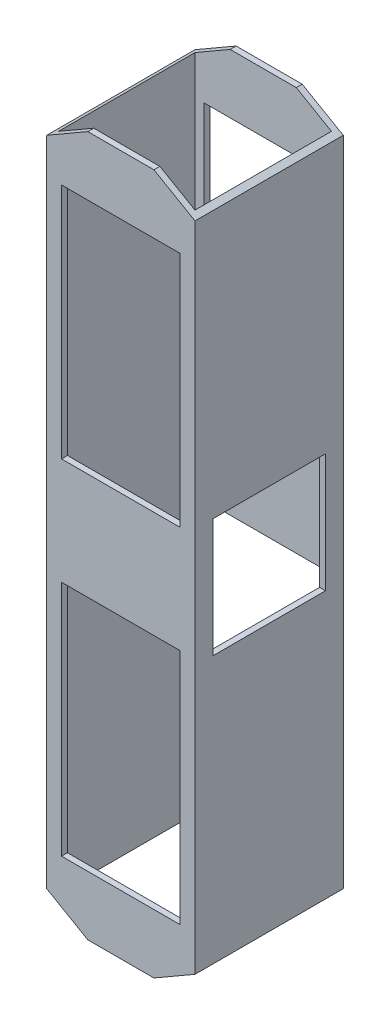
SolidWorks part; units mm, degrees
ref_plane "Alzado" through (0, 0, 0) normal (0, 0, 1) x (1, 0, 0)
ref_plane "Planta" through (0, 0, 0) normal (0, 1, 0) x (1, 0, 0)
ref_plane "Vista lateral" through (0, 0, 0) normal (1, 0, 0) x (0, 0, -1)
sketch "Croquis1" plane through (0, 0, 0) normal (0, 0, 1) x (1, 0, 0)
  line L0 (-35.0559, -98.8768) -> (-35.0559, 19.1232)
  line L3 (-35.0559, -98.8768) -> (-10.0559, -98.8768)
  line L4 (-10.0559, 19.1232) -> (-10.0559, -98.8768)
  line L5 (-35.0559, 19.1232) -> (-10.0559, 19.1232)
extrude "Saliente-Extruir1" add sketch "Croquis1" along normal blind 25
shell "Vaciado1" thickness 1 removed face at (-22.5559, -98.8768, 12.5) removed face at (-22.5559, 19.1232, 12.5)
sketch "Croquis2" plane through (0, 0, 25) normal (0, 0, 1) x (1, 0, 0)
  line L0 (-12.5559, -30.8768) -> (-32.5559, -30.8768)
  line L2 (-12.5559, -88.8768) -> (-12.5559, -48.8768)
  line L4 (-12.5559, -48.8768) -> (-32.5559, -48.8768)
  line L5 (-32.5559, -48.8768) -> (-32.5559, -88.8768)
  line L6 (-32.5559, -88.8768) -> (-22.5559, -88.8768)
  line L10 (-22.5559, -88.8768) -> (-12.5559, -88.8768)
  line L13 (-22.5559, 9.1232) -> (-12.5559, 9.1232)
  line L14 (-22.5559, 9.1232) -> (-32.5559, 9.1232)
  line L15 (-12.5559, 9.1232) -> (-12.5559, -30.8768)
  line L17 (-32.5559, -30.8768) -> (-32.5559, 9.1232)
extrude "Cortar-Extruir2" cut sketch "Croquis2" against normal blind 25
sketch "Croquis3" plane through (-10.0559, 0, 0) normal (1, 0, 0) x (0, 0, -1)
  line L7 (-22, -29.8768) -> (-22, -49.8768)
  line L8 (-3, -29.8768) -> (-3, -49.8768)
  line L9 (-3, -49.8768) -> (-22, -49.8768)
  line L10 (-3, -29.8768) -> (-22, -29.8768)
extrude "Cortar-Extruir3" cut sketch "Croquis3" against normal blind 1
chamfer "Chaflán1" distance 4 angle 60 2 edges at (-35.0559, 19.1232, 12.5) (-10.0559, 19.1232, 12.5) first distance on face at (-35.0559, -39.8768, 12.5) first distance on face at (-10.0559, -39.8768, 12.5)
chamfer "Chaflán2" distance 4 angle 60 2 edges at (-10.0559, -98.8768, 12.5) (-35.0559, -98.8768, 12.5) first distance on face at (-10.0559, -39.8768, 12.5) first distance on face at (-35.0559, -41.8768, 12.5)
